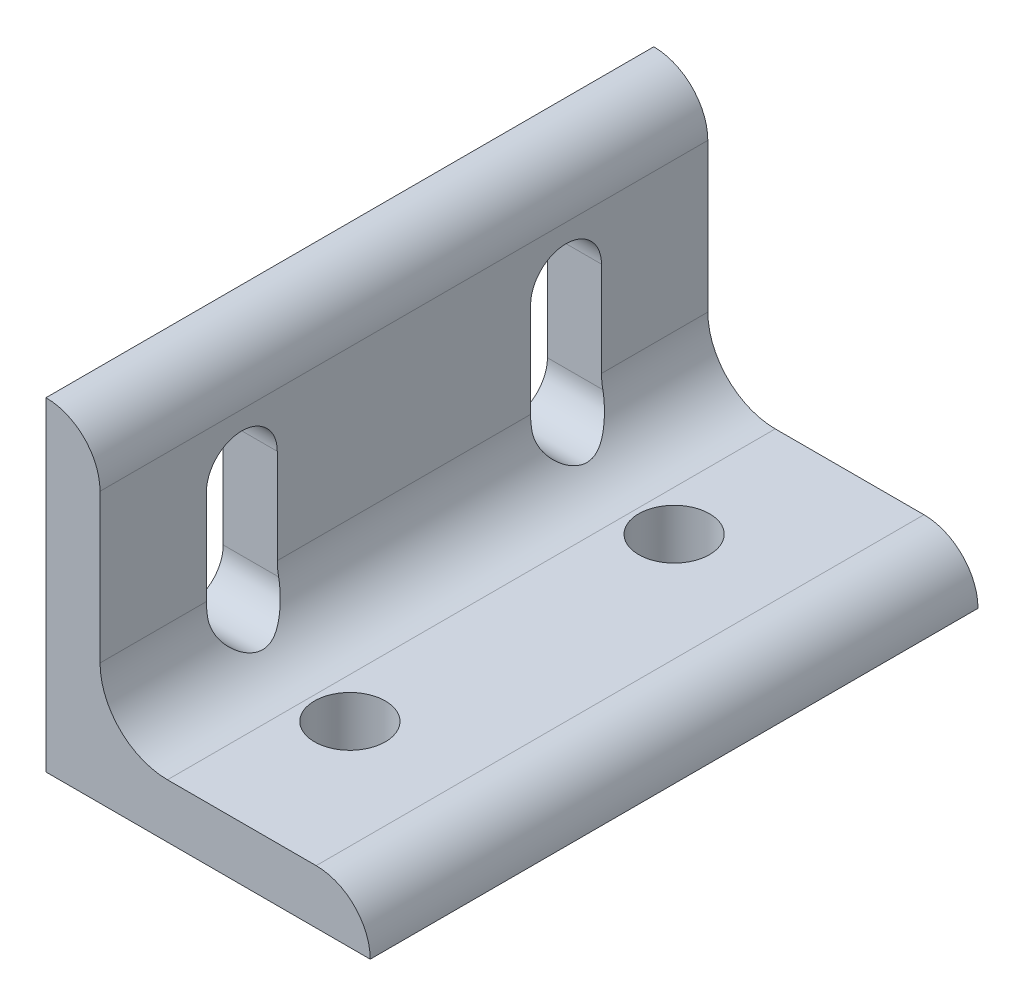
SolidWorks part; units mm, degrees
material "6105-T5 Aluminum"
ref_plane "Front Plane" through (0, 0, 0) normal (0, 0, 1) x (1, 0, 0)
ref_plane "Top Plane" through (0, 0, 0) normal (0, 1, 0) x (1, 0, 0)
ref_plane "Right Plane" through (0, 0, 0) normal (1, 0, 0) x (0, 0, -1)
sketch "Sketch2" plane through (0, 0, 0) normal (0, 0, 1) x (1, 0, 0)
  line L0 (0, 0) -> (0, 38.1)
  line L1 (38.1, 6.35) -> (38.1, 0)
  line L2 (6.35, 38.1) -> (6.35, 14.2748)
  line L3 (14.2748, 6.35) -> (38.1, 6.35)
  line L4 (0, 38.1) -> (6.35, 38.1)
  line L5 (38.1, 0) -> (0, 0)
  arc A2 (6.35, 14.2748) -> (14.2748, 6.35) centre (14.2748, 14.2748) ccw
  dimension "D3" = 38.1
  dimension "D4" = 7.9248
  dimension "D1" = 6.35
  dimension "D2" = 6.35
  dimension "D5" = 38.1
extrude "Boss-Extrude1" add sketch "Sketch2" along normal mid plane 71.4248
fillet "Fillet1" radius 6.35 2 edges at (38.1, 6.35, 0) (6.35, 38.1, 0)
sketch "Sketch3" plane through (0, 0, 0) normal (-1, 0, 0) x (0, 0, 1)
  line L0 (35.7124, 0) -> (-35.7124, 0) construction
  line L1 (-23.2156, 25.4) -> (-23.2156, 12.7)
  line L3 (-14.8844, 12.7) -> (-14.8844, 25.4)
  line L4 (0, 38.1) -> (0, 0) construction
  line L5 (35.7124, 38.1) -> (-35.7124, 38.1) construction
  line L6 (14.8844, 12.7) -> (14.8844, 25.4)
  line L8 (23.2156, 25.4) -> (23.2156, 12.7)
  arc A0 (-14.8844, 25.4) -> (-23.2156, 25.4) centre (-19.05, 25.4) ccw
  arc A1 (-23.2156, 12.7) -> (-14.8844, 12.7) centre (-19.05, 12.7) ccw
  arc A2 (23.2156, 12.7) -> (14.8844, 12.7) centre (19.05, 12.7) cw
  arc A3 (14.8844, 25.4) -> (23.2156, 25.4) centre (19.05, 25.4) cw
  dimension "D1" = 8.3312
  dimension "D2" = 25.4
  dimension "D3" = 12.7
  dimension "D4" = 19.05
extrude "Cut-Extrude1" cut sketch "Sketch3" against normal through all
sketch "Sketch4" plane through (0, 0, 0) normal (0, -1, 0) x (1, 0, 0)
  line L0 (19.05, 0) -> (26.0567, 0) construction
  line L1 (0, 35.7124) -> (0, -35.7124) construction
  circle A0 centre (19.05, -19.05) radius 4.1656
  circle A1 centre (19.05, 19.05) radius 4.1656
  dimension "D1" = 8.3312
  dimension "D2" = 19.05
  dimension "D5" = 19.05
extrude "Cut-Extrude2" cut sketch "Sketch4" against normal up to next
